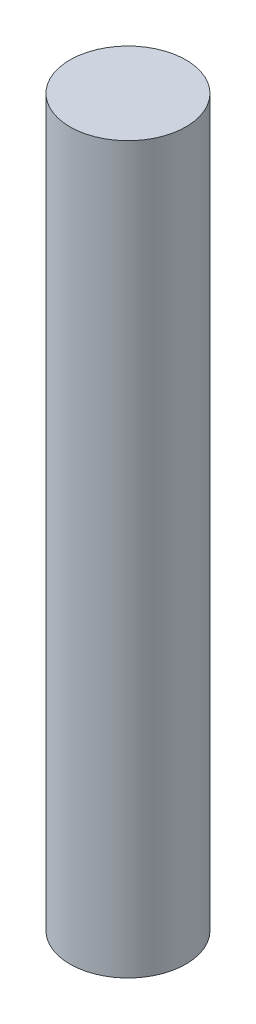
SolidWorks part; units mm, degrees
material "Acciaio al carbonio semplice"
ref_plane "Front Plane" through (0, 0, 0) normal (0, 0, 1) x (1, 0, 0)
ref_plane "Top Plane" through (0, 0, 0) normal (0, 1, 0) x (1, 0, 0)
ref_plane "Right Plane" through (0, 0, 0) normal (1, 0, 0) x (0, 0, -1)
other "Centro di massa"
sketch "Sketch1" plane through (0, 0, 0) normal (0, 1, 0) x (1, 0, 0)
  circle A0 centre (0, 0) radius 40
  point P0 (0, 0)
  dimension "D1" = 80
extrude "Boss-Extrude1" add sketch "Sketch1" along normal blind 500
sketch "Sketch2" plane through (0, 0, 0) normal (0, -1, 0) x (-1, 0, 0)
  circle A0 centre (0, 0) radius 30
  point P4 (0, 0)
  dimension "D1" = 60
extrude "Cut-Extrude1" cut sketch "Sketch2" against normal blind 10
sketch "Sketch3" plane through (0, 10, 0) normal (0, -1, 0) x (-1, 0, 0)
  circle A2 centre (0, 0) radius 35
  circle A3 centre (0, 0) radius 35
  dimension "D1" = 5
extrude "Cut-Extrude2" cut sketch "Sketch3" against normal blind 10
